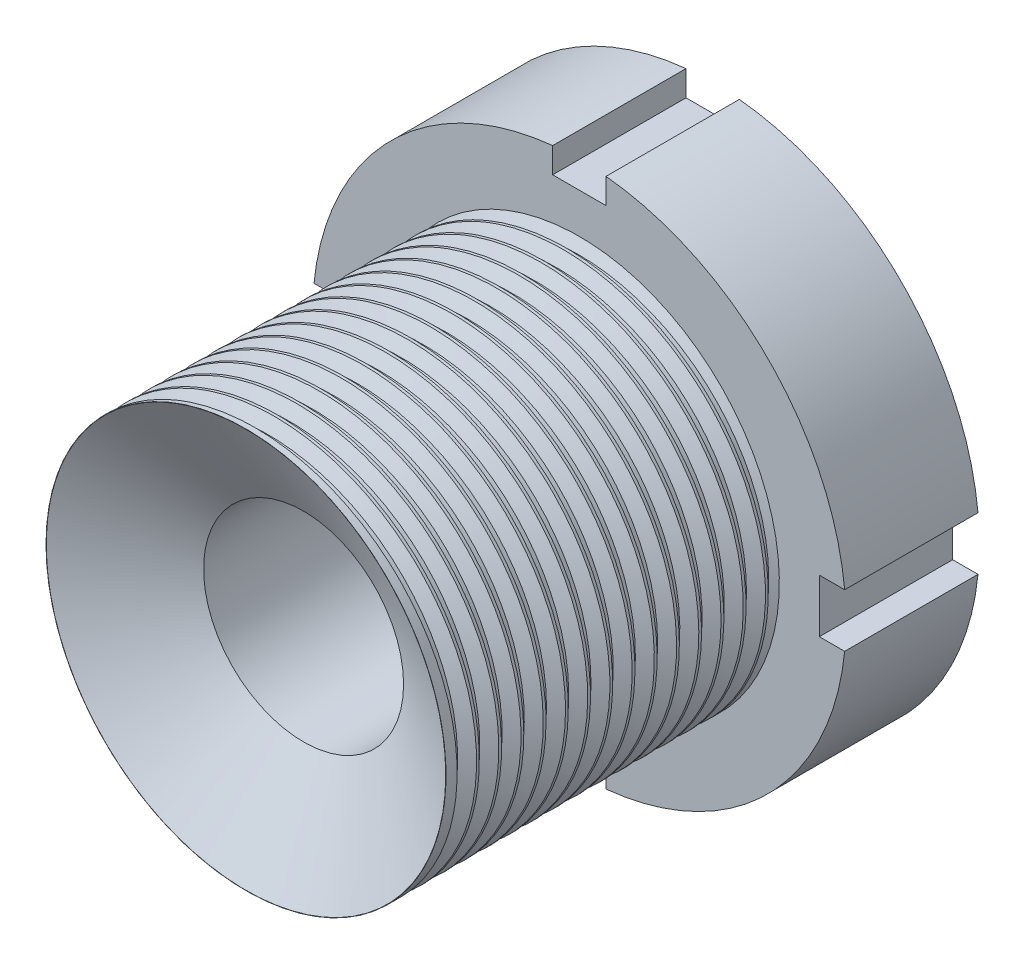
SolidWorks part; units mm, degrees
ref_plane "Front Plane" through (0, 0, 0) normal (0, 0, 1) x (1, 0, 0)
ref_plane "Top Plane" through (0, 0, 0) normal (0, 1, 0) x (1, 0, 0)
ref_plane "Right Plane" through (0, 0, 0) normal (1, 0, 0) x (0, 0, -1)
sketch "Sketch1" plane through (0, 0, 0) normal (0, 0, 1) x (1, 0, 0)
  circle A0 centre (0, 0) radius 12.7
extrude "Boss-Extrude1" add sketch "Sketch1" along normal blind 6.35
sketch "Sketch2" plane through (0, 0, 6.35) normal (0, 0, 1) x (1, 0, 0)
  circle A0 centre (0, 0) radius 9.525
extrude "Boss-Extrude2" add sketch "Sketch2" along normal blind 15.875
sketch "Sketch3" plane through (0, 0, 0) normal (0, 0, -1) x (-1, 0, 0)
  line L0 (0, 16.2971) -> (0, -20.8807) construction
  line L1 (-19.8621, 0) -> (21.9629, 0) construction
  line L2 (-1.27, 13.6959) -> (-1.27, 11.43)
  line L3 (-1.27, 11.43) -> (1.27, 11.43)
  line L4 (1.27, 13.6959) -> (1.27, 11.43)
  line L5 (-1.27, 13.6959) -> (1.27, 13.6959)
  line L6 (13.6959, 1.27) -> (13.6959, -1.27)
  line L7 (13.6959, -1.27) -> (11.43, -1.27)
  line L8 (11.43, 1.27) -> (11.43, -1.27)
  line L9 (13.6959, 1.27) -> (11.43, 1.27)
  line L10 (1.27, -13.6959) -> (-1.27, -13.6959)
  line L11 (-1.27, -13.6959) -> (-1.27, -11.43)
  line L12 (1.27, -11.43) -> (-1.27, -11.43)
  line L13 (1.27, -13.6959) -> (1.27, -11.43)
  line L14 (-13.6959, -1.27) -> (-13.6959, 1.27)
  line L15 (-13.6959, 1.27) -> (-11.43, 1.27)
  line L16 (-11.43, -1.27) -> (-11.43, 1.27)
  line L17 (-13.6959, -1.27) -> (-11.43, -1.27)
  point P11 (0, 11.43)
  point P26 (0, 0)
  dimension "D1" = 11.43
  dimension "D2" = 2.54
  dimension "D3" = 4
extrude "Cut-Extrude1" cut sketch "Sketch3" against normal through all
thread "Thread1" pitch 1.0583 method cut profile "Thread Profile1" start angle 0, offset 0, length 0, pitch 1.0583, diameter 19.05
ref_plane "Plane1" through (-9.525, 0, 22.225) normal (0, -1, 0) x (-1, 0, 0)
sketch "Thread Profile1" plane through (-9.525, 0, 22.225) normal (0, -1, 0) x (-1, 0, 0)
  line L0 (0, 0) -> (0, 1.0583) construction
  line L11 (0, 0) -> (0, 0.926)
  line L12 (0, 0.926) -> (-0.5728, 0.5953)
  line L13 (-0.5728, 0.5953) -> (-0.5728, 0.3307)
  line L15 (-0.5728, 0.3307) -> (0, 0)
  line L17 (-0.5728, 0.463) -> (0, 0.463) construction
  point P2 (0, 0)
  dimension "Pitch" = 1.0583
  dimension "Profile_Angle" = 60
  dimension "Profile_Land" = 0.2646
  dimension "Profile_Height" = 0.5728
hole_wizard "CSK for 3/8 Flat Head Machine Screw2" positions "Sketch12" profile "Sketch13" countersink size "3/8" standard "ANSI Inch" end condition up to next
sketch "Sketch12" plane through (0, 0, 22.225) normal (0, 0, 1) x (1, 0, 0)
  point P0 (0, 0)
sketch "Sketch13" plane through (0, 0, 22.225) normal (1, 0, 0) x (0, -1, 0)
  line L0 (0, 0) -> (0, 22.225)
  line L1 (0, 22.225) -> (4.7625, 22.225)
  line L2 (4.7625, 22.225) -> (4.7625, 2.7423)
  line L3 (4.7625, 2.7423) -> (9.5123, 0)
  line L5 (9.5123, 0) -> (0, 0)
  line L6 (-4.7625, 2.7423) -> (-9.5123, 0) construction
  line L11 (0, -6.35) -> (0, 107.95) construction
  dimension "Thru Hole Dia." = 9.525
  dimension "Thru Hole Depth" = 22.225
  dimension "Near C'Sink Dia." = 19.0246
  dimension "Near C'Sink Angle" = 120
